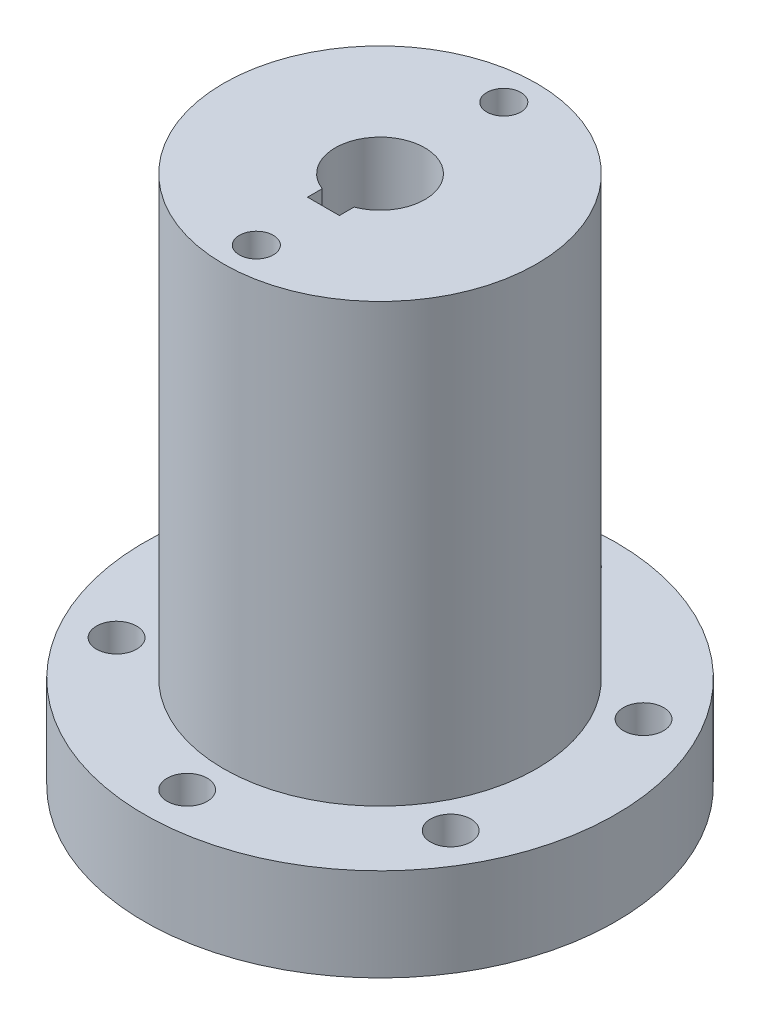
SolidWorks part; units mm, degrees
ref_plane "Front Plane" through (0, 0, 0) normal (0, 0, 1) x (1, 0, 0)
ref_plane "Top Plane" through (0, 0, 0) normal (0, 1, 0) x (1, 0, 0)
ref_plane "Right Plane" through (0, 0, 0) normal (1, 0, 0) x (0, 0, -1)
sketch "Sketch1" plane through (0, 0, 0) normal (0, 1, 0) x (1, 0, 0)
  circle A0 centre (0, 0) radius 25.3
extrude "Boss-Extrude1" add sketch "Sketch1" along normal blind 8.5
sketch "Sketch2" plane through (0, 8.5, 0) normal (0, 1, 0) x (1, 0, 0)
  circle A0 centre (0, 0) radius 25.3
extrude "Boss-Extrude2" add sketch "Sketch2" along normal blind 57.15
sketch "Sketch7" plane through (0, 65.65, 0) normal (0, 1, 0) x (1, 0, 0)
  circle A0 centre (0, 0) radius 25.3
extrude "Boss-Extrude4" add sketch "Sketch7" along normal blind 15
sketch "Sketch5" plane through (0, 0, 0) normal (0, -1, 0) x (1, 0, 0)
  line L1 (-2.575, 9.15) -> (2.575, 9.15)
  line L2 (-2.575, 9.15) -> (-2.575, 4)
  line L3 (-2.575, 4) -> (2.575, 4)
  line L4 (2.575, 9.15) -> (2.575, 4)
  circle A0 centre (0, 0) radius 7.25
  dimension "D1" = 5.15
  dimension "D2" = 5.15
  dimension "D3" = 9.15
  dimension "D4" = 2.575
extrude "Cut-Extrude3" cut sketch "Sketch5" against normal blind 115 contours L2 A0 L4 L3 | L4 A0 L2 L3 | A0 L4 L1 L2 region at (0, 0, 8.1175) region at (0, 0, 5.5505) region at (0, 0, -0.5929)
sketch "Sketch6" plane through (0, 0, 0) normal (0, -1, 0) x (1, 0, 0)
  circle A0 centre (0, 0) radius 38.1
extrude "Boss-Extrude3" add sketch "Sketch6" along normal blind 15
sketch "Sketch9" plane through (0, 0, 0) normal (0, 1, 0) x (1, 0, 0)
  line L1 (0, 31.1769) -> (-27, 15.5885)
  line L2 (-27, 15.5885) -> (-27, -15.5885)
  line L3 (-27, -15.5885) -> (0, -31.1769)
  line L4 (0, -31.1769) -> (27, -15.5885)
  line L5 (27, -15.5885) -> (27, 15.5885)
  line L6 (27, 15.5885) -> (0, 31.1769)
  circle A0 centre (0, 0) radius 27 construction
  circle A1 centre (0, 31.1769) radius 3.25
  circle A2 centre (-27, 15.5885) radius 3.25
  circle A3 centre (-27, -15.5885) radius 3.25
  circle A4 centre (0, -31.1769) radius 3.25
  circle A5 centre (27, -15.5885) radius 3.25
  circle A6 centre (27, 15.5885) radius 3.25
extrude "Cut-Extrude4" cut sketch "Sketch9" against normal blind 20 contours L1 A2 L2 | L2 A2 L1 | L6 A1 L1 | L1 A1 L6 | L5 A6 L6 | L6 A6 L5 | L4 A5 L5 | L5 A5 L4 | L3 A4 L4 | L4 A4 L3 | L2 A3 L3 | L3 A3 L2 region at (0, 0, -29.3851) region at (0, 0, -32.0728) region at (-25.4482, 0, -14.6925) region at (-27.7759, 0, -16.0364) region at (27.7759, 0, -16.0364) region at (25.4482, 0, -14.6925) region at (-25.4482, 0, 14.6925) region at (-27.7759, 0, 16.0364) region at (27.7759, 0, 16.0364) region at (25.4482, 0, 14.6925) region at (0, 0, 29.3851) region at (0, 0, 32.0728)
sketch "Sketch10" plane through (0, 80.65, 0) normal (0, 1, 0) x (1, 0, 0)
  circle A0 centre (0, 20) radius 2.75
  circle A1 centre (0, -20) radius 2.75
  arc A2 (2.575, -6.7773) -> (-2.575, -6.7773) centre (0, 0) ccw construction
  dimension "D1" = 20
  dimension "D2" = 20
extrude "Cut-Extrude6" cut sketch "Sketch10" against normal blind 129
sketch "Sketch11" plane through (0, 80.65, 0) normal (0, 1, 0) x (1, 0, 0)
  line L0 (-2.575, -6.7773) -> (-2.575, -9.15)
  line L1 (-2.575, -9.15) -> (2.575, -9.15)
  line L2 (2.575, -9.15) -> (2.575, -6.7773)
  circle A0 centre (0, 0) radius 7.25
  arc M3 (-2.575, -6.7773) -> (2.575, -6.7773) centre (0, 0) cw
  line M4 (2.575, -6.7773) -> (2.575, -9.15)
  line M5 (2.575, -9.15) -> (-2.575, -9.15)
  line M6 (-2.575, -9.15) -> (-2.575, -6.7773)
extrude "Boss-Extrude5" add sketch "Sketch11" against normal blind 93 contours A0 M3 | A0 M6 M5 M4 region at (0, 80.65, 8.1175) region at (0, 80.65, 0)
extrude "Cut-Extrude7" cut sketch "Sketch11<3>" against normal blind 40 contours A0 M3 | A0 M6 M5 M4 region at (0, 80.65, 8.1175) region at (0, 80.65, 0)
sketch "Sketch11<3>" plane through (0, 80.65, 0) normal (0, 1, 0) x (1, 0, 0) same geometry as "Sketch11"
sketch "Sketch12" plane through (0, 80.65, 0) normal (0, 1, 0) x (1, 0, 0)
  circle A0 centre (0, 0) radius 25.3
extrude "Cut-Extrude8" cut sketch "Sketch12" against normal blind 10
